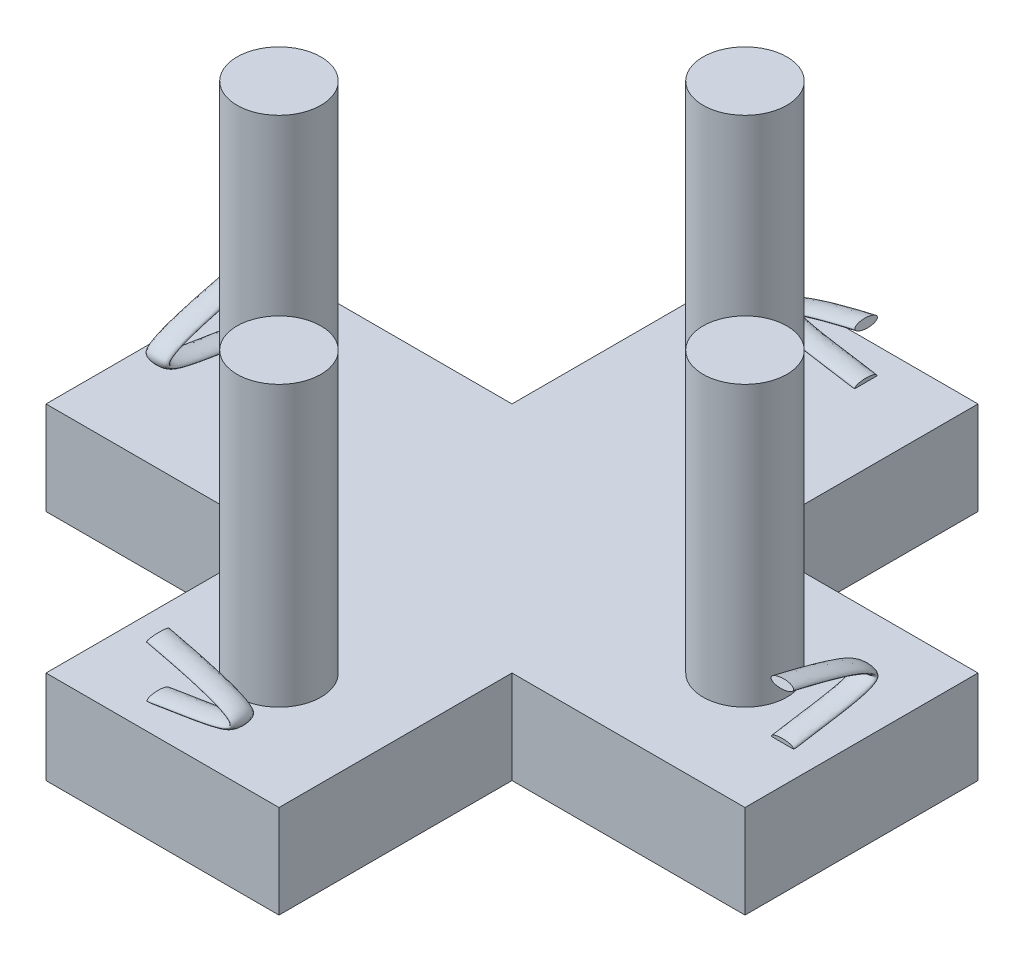
SolidWorks part; units mm, degrees
ref_plane "Front Plane" through (0, 0, 0) normal (0, 0, 1) x (1, 0, 0)
ref_plane "Top Plane" through (0, 0, 0) normal (0, 1, 0) x (1, 0, 0)
ref_plane "Right Plane" through (0, 0, 0) normal (1, 0, 0) x (0, 0, -1)
sketch "Sketch1" plane through (0, 0, 0) normal (0, 1, 0) x (1, 0, 0)
  line L0 (-8.3487, -10.4521) -> (-8.3487, -4.1021)
  line L1 (-8.3487, -4.1021) -> (-1.9987, -4.1021)
  line L2 (-1.9987, -4.1021) -> (-1.9987, -10.4521)
  line L3 (-1.9987, -10.4521) -> (4.3513, -10.4521)
  line L4 (4.3513, -10.4521) -> (4.3513, -16.8021)
  line L5 (4.3513, -16.8021) -> (-1.9987, -16.8021)
  line L6 (-1.9987, -16.8021) -> (-1.9987, -23.1521)
  line L7 (-1.9987, -23.1521) -> (-8.3487, -23.1521)
  line L8 (-8.3487, -23.1521) -> (-8.3487, -16.8021)
  line L9 (-8.3487, -16.8021) -> (-14.6987, -16.8021)
  line L10 (-14.6987, -16.8021) -> (-14.6987, -10.4521)
  line L11 (-14.6987, -10.4521) -> (-8.3487, -10.4521)
  dimension "D1" = 6.35
  dimension "D2" = 6.35
  dimension "D3" = 6.35
  dimension "D4" = 6.35
  dimension "D5" = 6.35
  dimension "D6" = 6.35
  dimension "D7" = 6.35
  dimension "D8" = 6.35
  dimension "D9" = 6.35
  dimension "D10" = 6.35
extrude "body" add sketch "Sketch1" along normal blind 2.54
sketch "Sketch2" plane through (0, 2.54, 0) normal (0, 1, 0) x (1, 0, 0)
  line L0 (-8.3487, -10.4521) -> (-14.6987, -10.4521) construction
  line L1 (-1.9987, -23.1521) -> (-1.9987, -16.8021) construction
  line L2 (-1.9987, -16.8021) -> (4.3513, -16.8021) construction
  line L3 (-1.9987, -10.4521) -> (-1.9987, -4.1021) construction
  line L4 (-1.9987, -4.1021) -> (-8.3487, -4.1021) construction
  line L5 (-14.6987, -10.4521) -> (-14.6987, -16.8021) construction
  line L6 (-8.3487, -23.1521) -> (-1.9987, -23.1521) construction
  line L7 (4.3513, -16.8021) -> (4.3513, -10.4521) construction
  circle A0 centre (-5.1737, -7.2771) radius 1.143
  circle A1 centre (1.1763, -13.6271) radius 1.143
  circle A2 centre (-5.1737, -19.9771) radius 1.143
  circle A3 centre (-11.5237, -13.6271) radius 1.143
  dimension "D1" = 2.286
  dimension "D2" = 2.286
  dimension "D3" = 2.286
  dimension "D4" = 2.286
  dimension "D5" = 3.175
  dimension "D6" = 3.175
  dimension "D7" = 3.175
  dimension "D8" = 3.175
  dimension "D9" = 3.175
  dimension "D10" = 3.175
  dimension "D11" = 3.175
  dimension "D12" = 3.175
extrude "pegs" add sketch "Sketch2" along normal blind 7.62
ref_point "top center"
ref_point "bottom center"
ref_axis "center axis" through (-5.1737, 0, 13.6271) along (0, 1, 0)
ref_plane "spring plane" through (0, 0, 5.1181) normal (0, 0, -1) x (-1, 0, 0)
sketch "Sketch3" plane through (0, 0, 5.1181) normal (0, 0, -1) x (-1, 0, 0)
  line L0 (1.9987, 2.54) -> (8.3487, 2.54) construction
  line L2 (4.0307, 10.16) -> (4.0307, 2.54) construction
  spline S0 degree 3 poles (4.0369, 2.54) (5.7469, 2.854) (8.1804, 2.9787) (4.0307, 3.941) knots 0 0 0 0 1 1 1 1
ref_plane "spring cross section" through (-4.0369, 0, 0) normal (1, 0, 0) x (0, 0, -1)
sketch "Sketch4" plane through (-4.0369, 0, 0) normal (1, 0, 0) x (0, 0, -1)
  ellipse E0 centre (-5.1181, 2.54) end of major axis (-4.8133, 2.54) minor radius 0.1016
sweep "spring" add profiles "Sketch4" path "Sketch3"
pattern_circular "moar springs" count 4 over 360 about axis through (-5.1737, 0, 13.6271) along (0, 1, 0) of "spring"
